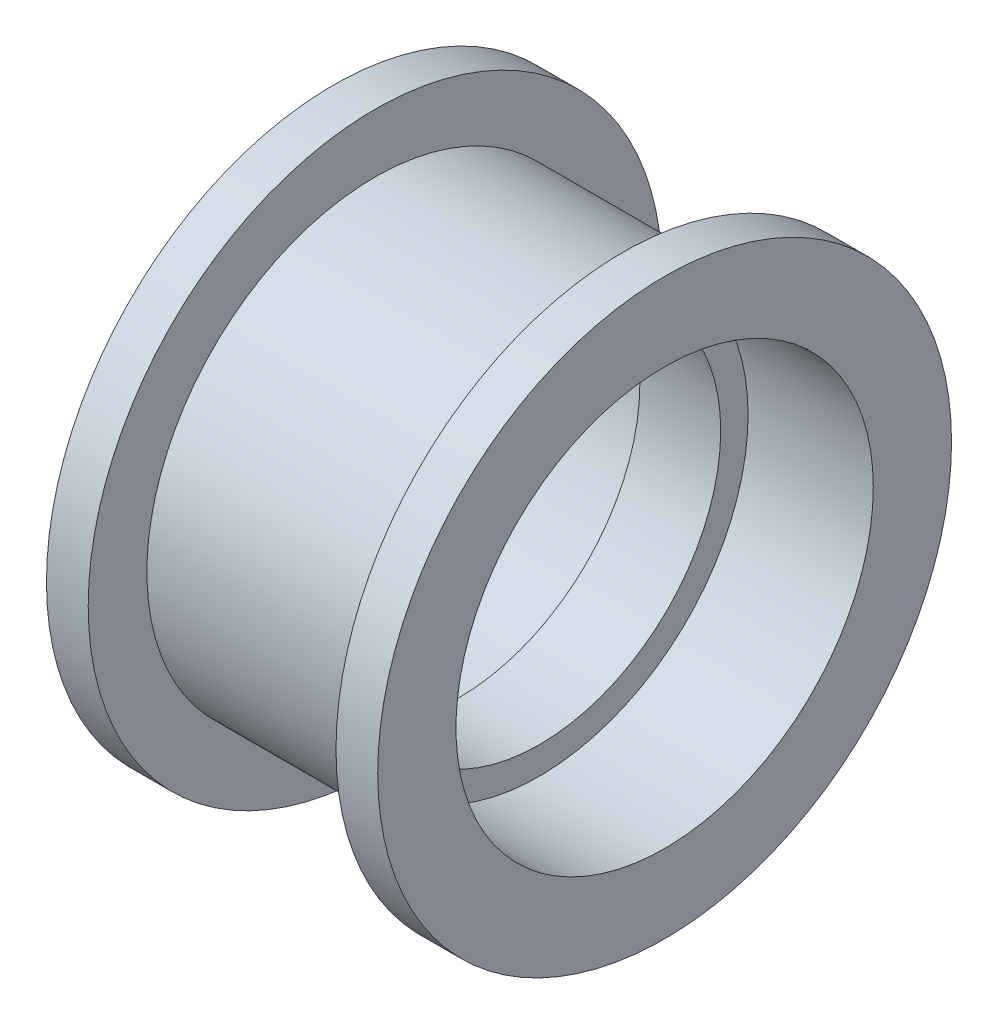
SolidWorks part; units mm, degrees
material "Delrin 2700 NC010, Low Viscosity Acetal Copolymer (SS)"
ref_plane "Front Plane" through (0, 0, 0) normal (0, 0, 1) x (1, 0, 0)
ref_plane "Top Plane" through (0, 0, 0) normal (0, 1, 0) x (1, 0, 0)
ref_plane "Right Plane" through (0, 0, 0) normal (1, 0, 0) x (0, 0, -1)
sketch "Sketch1" plane through (0, 0, 0) normal (0, 0, 1) x (1, 0, 0)
  line L0 (1.55, 6.95) -> (-1.55, 6.95)
  line L1 (-1.55, 6.95) -> (-1.55, 8)
  line L2 (-1.55, 8) -> (-6.35, 8)
  line L3 (-6.35, 8) -> (-6.35, 11)
  line L4 (-6.35, 11) -> (-4.75, 11)
  line L5 (-4.75, 8.75) -> (4.75, 8.75)
  line L6 (0, 8.75) -> (0, 6.95) construction
  line L7 (-4.75, 11) -> (-4.75, 8.75)
  line L8 (6.35, 8) -> (6.35, 11)
  line L9 (1.55, 8) -> (6.35, 8)
  line L10 (1.55, 6.95) -> (1.55, 8)
  line L11 (0, 0) -> (-12.6359, 0) construction
  line L12 (4.75, 11) -> (4.75, 8.75)
  line L13 (6.35, 11) -> (4.75, 11)
  dimension "D1" = 1.6
  dimension "8.64" = 13.9
  dimension "D2" = 16
  dimension "D3" = 17.5
  dimension "D4" = 3.1
  dimension "D5" = 22
  dimension "D6" = 12.7
revolve "Revolve1" add sketch "Sketch1" angle 360 about L11
ref_plane "Mid Idler Plane" through (0, 0, 0) normal (1, 0, 0) x (0, 0, -1)
ref_plane "Plane1" through (0, 8.75, 0) normal (0, 1, 0) x (1, 0, 0)
ref_plane "Plane2" through (0, 10.25, 0) normal (0, 1, 0) x (1, 0, 0)
